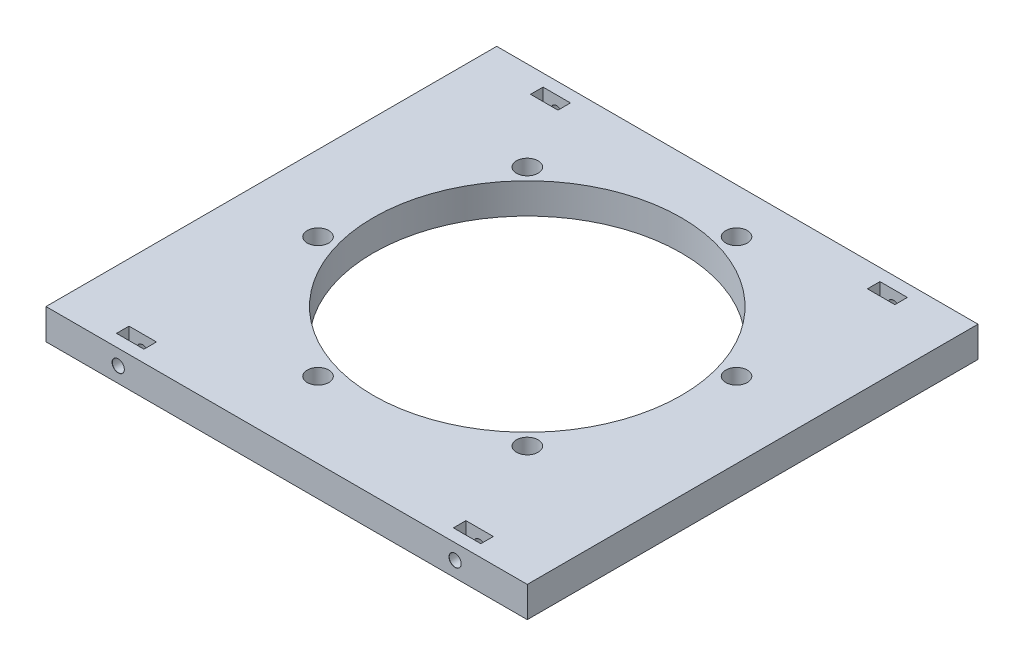
SolidWorks part; units mm, degrees
material "6061 Alloy"
ref_plane "Front Plane" through (0, 0, 0) normal (0, 0, 1) x (1, 0, 0)
ref_plane "Top Plane" through (0, 0, 0) normal (0, 1, 0) x (1, 0, 0)
ref_plane "Right Plane" through (0, 0, 0) normal (1, 0, 0) x (0, 0, -1)
sketch "Sketch1" plane through (0, 0, 0) normal (0, 1, 0) x (1, 0, 0)
  line L1 (-50, -50) -> (50, -50)
  line L2 (-50, -50) -> (-50, 50)
  line L3 (-50, 50) -> (50, 50)
  line L4 (50, -50) -> (50, 50)
  line L5 (-50, -50) -> (50, 50) construction
  line L6 (-50, 50) -> (50, -50) construction
  circle A1 centre (0, 0) radius 39.5
  arc A5 (-25.1023, 25.1023) -> (9.1881, 34.2904) centre (0, 0) cw
  arc A7 (9.1881, 34.2904) -> (-34.2904, -9.1881) centre (0, 0) ccw
  arc A9 (-34.2904, -9.1881) -> (-9.1881, -34.2904) centre (0, 0) ccw
  arc A11 (-9.1881, -34.2904) -> (25.1023, -25.1023) centre (0, 0) ccw
  circle A13 centre (0, 0) radius 32
  arc A14 (25.1023, -25.1023) -> (34.2904, 9.1881) centre (0, 0) ccw
extrude "Boss-Extrude3" add sketch "Sketch1" along normal blind 6.35 contours L1 L4 L3 L2 A1 | A1 A13 region at (-48.5858, 0, 0) region at (-38.3828, 0, 0)
hole_wizard "M4 Clearance Hole2" positions "Sketch6" profile "Sketch7" hole size "M4" standard "ANSI Metric" end condition through all
sketch "Sketch6" plane through (0, 0, 0) normal (0, -1, 0) x (-1, 0, 0)
  point P0 (-9.1881, 34.2904)
  point P3 (25.1023, 25.1023)
  point P6 (34.2904, -9.1881)
  point P9 (9.1881, -34.2904)
  point P12 (-25.1023, -25.1023)
  point P15 (-34.2904, 9.1881)
sketch "Sketch7" plane through (9.1881, 0, -34.2904) normal (1, 0, 0) x (0, 0, -1)
  line L0 (0, 0) -> (0, 6.35)
  line L1 (0, 6.35) -> (2.25, 6.35)
  line L2 (2.25, 6.35) -> (2.25, 0.025)
  line L3 (2.25, 0.025) -> (2.275, 0)
  line L5 (2.275, 0) -> (0, 0)
  line L6 (-2.25, 0.025) -> (-2.275, 0) construction
  line L11 (0, -6.35) -> (0, 107.95) construction
  dimension "Thru Hole Dia." = 4.5
  dimension "Thru Hole Depth" = 6.35
  dimension "Near C'Sink Dia." = 4.55
  dimension "Near C'Sink Angle" = 90
sketch "Sketch13" plane through (0, 6.35, 0) normal (0, 1, 0) x (1, 0, 0)
  line L0 (-50, -50) -> (-46.1091, -46.1091)
  line L1 (-46.1091, -46.1091) -> (-68.3017, -23.9166)
  line L2 (-46.1091, -46.1091) -> (-23.9166, -68.3017)
sketch "Sketch16" plane through (0, 6.35, 0) normal (0, 1, 0) x (1, 0, 0)
  line L0 (-50, -50) -> (-55, -50)
  line L1 (-50, -50) -> (50, -50) construction
  line L2 (-55, -50) -> (-55, -70)
  line L3 (-50, -50) -> (-75, -50)
  line L4 (-75, -50) -> (-75, -70)
  line L5 (-75, -70) -> (-55, -70)
  line L6 (-50, 50) -> (-55, 50)
  line L7 (-50, 50) -> (50, 50) construction
  line L8 (50, 50) -> (55, 50)
  line L9 (50, -50) -> (55, -50)
  line L11 (-55, 50) -> (-75, 50)
  line L12 (-55, 50) -> (-55, 70)
  line L13 (-55, 70) -> (-75, 70)
  line L14 (-75, 50) -> (-75, 70)
  line L15 (55, 50) -> (75, 50)
  line L16 (55, 50) -> (55, 70)
  line L17 (55, 70) -> (75, 70)
  line L18 (75, 50) -> (75, 70)
  line L19 (55, -50) -> (75, -50)
  line L20 (55, -50) -> (55, -70)
  line L21 (55, -70) -> (75, -70)
  line L22 (75, -50) -> (75, -70)
sketch "Sketch23" plane through (0, 6.35, 0) normal (0, 1, 0) x (1, 0, 0)
  line L0 (-50, -50) -> (-50, -55)
  line L1 (-50, -50) -> (-50, 50) construction
  line L2 (-50, 50) -> (-50, 55)
  line L3 (85, 50) -> (50, 55)
  line L4 (-50, 50) -> (50, 50) construction
  line L5 (50, -50) -> (50, 50) construction
  line L6 (50, -50) -> (50, -55)
  line L8 (-50, 55) -> (-70, 55)
  line L9 (-50, 55) -> (-50, 75)
  line L10 (-50, 75) -> (-70, 75)
  line L11 (-70, 55) -> (-70, 75)
  line L12 (50, 55) -> (70, 55)
  line L13 (50, 55) -> (50, 75)
  line L14 (50, 75) -> (70, 75)
  line L15 (70, 55) -> (70, 75)
  line L16 (50, -55) -> (70, -55)
  line L17 (50, -55) -> (50, -75)
  line L18 (50, -75) -> (70, -75)
  line L19 (70, -55) -> (70, -75)
  line L20 (-50, -55) -> (-70, -55)
  line L21 (-50, -55) -> (-50, -75)
  line L22 (-50, -75) -> (-70, -75)
  line L23 (-70, -55) -> (-70, -75)
sketch "Sketch24" plane through (0, 0, 50) normal (0, 0, 1) x (1, 0, 0)
  line L0 (-50, 3.175) -> (-35, 3.175)
  line L1 (-50, 6.35) -> (-50, 0) construction
  line L2 (50, 3.175) -> (35, 3.175)
  line L3 (50, 6.35) -> (50, 0) construction
hole_wizard "Tap Drill for M3x0.5 Tap2" positions "Sketch27" profile "Sketch28" hole size "M3x0.5" standard "ANSI Metric"
sketch "Sketch27" plane through (0, 0, 50) normal (0, 0, 1) x (1, 0, 0)
  point P0 (-35, 3.175)
  point P3 (35, 3.175)
sketch "Sketch28" plane through (-35, 3.175, 50) normal (1, 0, 0) x (0, -1, 0)
  line L0 (0, 0) -> (0, 10)
  line L1 (0, 10) -> (1.25, 9.2489)
  line L2 (1.25, 9.2489) -> (1.25, 0.025)
  line L3 (1.25, 0.025) -> (1.275, 0)
  line L5 (1.275, 0) -> (0, 0)
  line L6 (-1.25, 0.025) -> (-1.275, 0) construction
  line L10 (0, 10) -> (-1.25, 9.2489) construction
  line L11 (0, -6.35) -> (0, 107.95) construction
  dimension "Hole Dia." = 2.5
  dimension "Hole Depth" = 10
  dimension "Near C'Sink Dia." = 2.55
  dimension "Near C'Sink Angle" = 90
  dimension "Drill Angle" = 118
sketch "Sketch29" plane through (0, 0, -50) normal (0, 0, -1) x (-1, 0, 0)
  line L0 (-50, 3.175) -> (-35, 3.175)
  line L1 (50, 3.175) -> (35, 3.175)
sketch "Sketch32" plane through (0, 6.35, 0) normal (0, 1, 0) x (1, 0, 0)
  line L0 (50, -50) -> (50, 50) construction
  line L1 (-50, 50) -> (50, 50)
  line L2 (-50, 50) -> (-50, 43.65)
  line L3 (-50, 43.65) -> (50, 43.65)
  line L4 (50, 50) -> (50, 43.65)
extrude "Cut-Extrude1" cut sketch "Sketch32" against normal blind 10
sketch "Sketch33" plane through (0, 0, -43.65) normal (0, 0, -1) x (-1, 0, 0)
  line L0 (-50, 3.175) -> (-35, 3.175)
  line L1 (-50, 0) -> (-50, 6.35) construction
  line L2 (50, 3.175) -> (35, 3.175)
  line L3 (50, 0) -> (50, 6.35) construction
hole_wizard "Tap Drill for M3x0.5 Tap4" positions "Sketch34" profile "Sketch35" hole size "M3x0.5" standard "ANSI Metric"
sketch "Sketch34" plane through (0, 0, -43.65) normal (0, 0, -1) x (-1, 0, 0)
  point P0 (-35, 3.175)
  point P3 (35, 3.175)
sketch "Sketch35" plane through (35, 3.175, -43.65) normal (1, 0, 0) x (0, 1, 0)
  line L0 (0, 0) -> (0, 10)
  line L1 (0, 10) -> (1.25, 9.2489)
  line L2 (1.25, 9.2489) -> (1.25, 0.025)
  line L3 (1.25, 0.025) -> (1.275, 0)
  line L5 (1.275, 0) -> (0, 0)
  line L6 (-1.25, 0.025) -> (-1.275, 0) construction
  line L10 (0, 10) -> (-1.25, 9.2489) construction
  line L11 (0, -6.35) -> (0, 107.95) construction
  dimension "Hole Dia." = 2.5
  dimension "Hole Depth" = 10
  dimension "Near C'Sink Dia." = 2.55
  dimension "Near C'Sink Angle" = 90
  dimension "Drill Angle" = 118
sketch "Sketch36" plane through (0, 6.35, 0) normal (0, 1, 0) x (1, 0, 0)
  line L0 (-50, -50) -> (50, -50) construction
  line L1 (-37.85, -47.5) -> (-32.15, -47.5)
  line L2 (-37.85, -47.5) -> (-37.85, -44.9)
  line L3 (-37.85, -44.9) -> (-32.15, -44.9)
  line L4 (-32.15, -47.5) -> (-32.15, -44.9)
  line L5 (-37.85, -47.5) -> (-32.15, -44.9) construction
  line L6 (-37.85, -44.9) -> (-32.15, -47.5) construction
  line L7 (32.15, -47.5) -> (37.85, -47.5)
  line L8 (32.15, -47.5) -> (32.15, -44.9)
  line L9 (32.15, -44.9) -> (37.85, -44.9)
  line L10 (37.85, -47.5) -> (37.85, -44.9)
  line L11 (32.15, -47.5) -> (37.85, -44.9) construction
  line L12 (32.15, -44.9) -> (37.85, -47.5) construction
  line L13 (33.75, 43.625) -> (36.25, 43.625) construction
  line L14 (-36.25, 43.625) -> (-33.75, 43.625) construction
  line L15 (33.75, 43.625) -> (36.25, 43.625) construction
  line L16 (-36.25, 43.625) -> (-33.75, 43.625) construction
  line L17 (-36.275, -50) -> (-33.725, -50) construction
  line L18 (-36.275, -50) -> (-33.725, -50) construction
  line L19 (36.25, -49.975) -> (33.75, -49.975) construction
  line L20 (36.25, -49.975) -> (33.75, -49.975) construction
  line L22 (37.85, 41.125) -> (32.15, 41.125)
  line L23 (37.85, 41.125) -> (37.85, 38.525)
  line L24 (37.85, 38.525) -> (32.15, 38.525)
  line L25 (32.15, 41.125) -> (32.15, 38.525)
  line L26 (37.85, 41.125) -> (32.15, 38.525) construction
  line L27 (37.85, 38.525) -> (32.15, 41.125) construction
  line L28 (-32.15, 38.525) -> (-37.85, 38.525)
  line L29 (-32.15, 38.525) -> (-32.15, 41.125)
  line L30 (-32.15, 41.125) -> (-37.85, 41.125)
  line L31 (-37.85, 38.525) -> (-37.85, 41.125)
  line L32 (-32.15, 38.525) -> (-37.85, 41.125) construction
  line L33 (-32.15, 41.125) -> (-37.85, 38.525) construction
  point P0 (-35, -46.2)
  point P5 (35, -46.2)
  point P12 (-35, 39.825)
  point P14 (-35, -50)
  point P17 (35, -49.975)
  point P25 (35, 39.825)
  point P33 (-35, 43.625)
  point P35 (35, 43.625)
  dimension "D1" = 2.5
  dimension "D2" = 2.6
  dimension "D3" = 5.7
  dimension "D4" = 2.5
extrude "Cut-Extrude2" cut sketch "Sketch36" against normal through all
